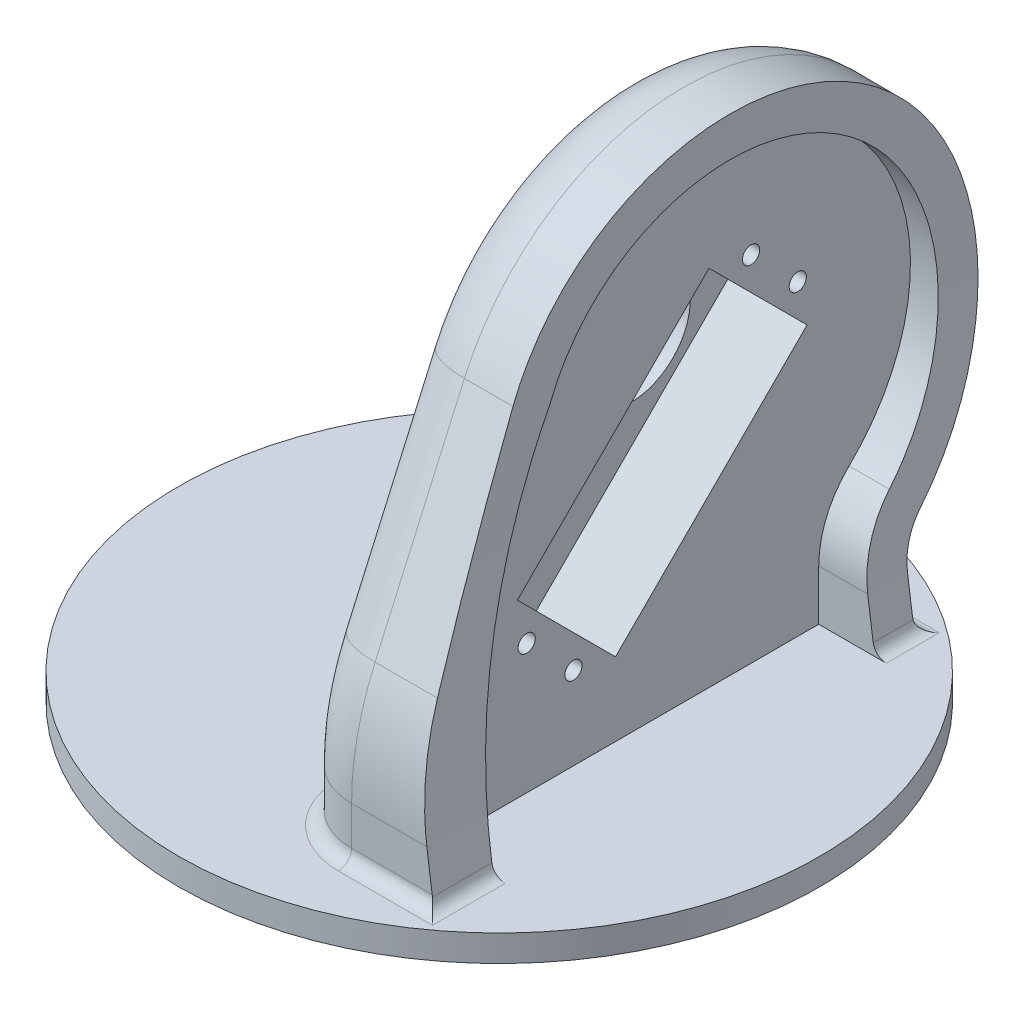
SolidWorks part; units mm, degrees
ref_plane "Front Plane" through (0, 0, 0) normal (0, 0, 1) x (1, 0, 0)
ref_plane "Top Plane" through (0, 0, 0) normal (0, 1, 0) x (1, 0, 0)
ref_plane "Right Plane" through (0, 0, 0) normal (1, 0, 0) x (0, 0, -1)
sketch "Sketch1" plane through (0, 0, 0) normal (0, 1, 0) x (1, 0, 0)
  line L0 (0, -7.25) -> (0, 7.25) construction
  circle A0 centre (0, 0) radius 48.5
  circle A1 centre (0, 7.25) radius 1.5
  circle A2 centre (0, -7.25) radius 1.5
  point P6 (0, 0)
  dimension "D2" = 97
  dimension "D3" = 3
  dimension "D1" = 14.5
extrude "Boss-Extrude3" add sketch "Sketch1" along normal blind 4
sketch "Sketch2" plane through (0, 4, 0) normal (0, 1, 0) x (1, 0, 0)
  line L0 (0, 11.1571) -> (0, -11.7638) construction
  circle A1 centre (0, 0) radius 3.75
  dimension "D1" = 7.5
sketch "Sketch3" plane through (0, 0, 0) normal (1, 0, 0) x (0, 0, -1)
  line L0 (30.34, 4) -> (-30.34, 4)
  line L1 (30.34, 4) -> (30.34, 11.64)
  line L2 (48.5, 4) -> (-48.5, 4) construction
  line L3 (-30.34, 4) -> (-30.34, 11.86)
  line L4 (-27.3065, 26.1616) -> (-13.7924, 56.5853)
  arc A0 (30.34, 11.64) -> (34.9356, 22.445) centre (45.34, 11.64) cw
  arc A1 (34.9356, 22.445) -> (-13.7924, 56.5853) centre (13.91, 44.28) ccw
  arc A2 (-30.34, 11.86) -> (-27.3065, 26.1616) centre (4.89, 11.86) cw
  circle A3 centre (13.91, 44.28) radius 9
  point P3 (0, 4)
  dimension "D3" = 15
  dimension "D5" = 35.23
  dimension "D6" = 18
  dimension "D1" = 60.68
  dimension "D2" = 7.64
  dimension "D4" = 7.86
  dimension "D7" = 13.91
  dimension "D8" = 40.28
extrude "Boss-Extrude4" add sketch "Sketch3" along normal blind 14 from offset 4
sketch "Sketch5" plane through (0, 0, 0) normal (1, 0, 0) x (0, 0, -1)
  line L0 (-0.41, 15.11) -> (28.5814, 44.1014)
  line L1 (-0.41, 15.11) -> (-15.2592, 29.9592)
  line L2 (28.5814, 44.1014) -> (13.7321, 58.9506)
  line L3 (-15.2592, 29.9592) -> (13.7321, 58.9506)
  line L4 (14.0857, 29.6057) -> (-0.7636, 44.4549) construction
  line L5 (48.5, 4) -> (-48.5, 4) construction
  line L6 (6.6611, 37.0303) -> (23.6316, 54.0009) construction
  line L7 (27.1672, 50.4653) -> (20.0961, 57.5364) construction
  circle A0 centre (27.1672, 50.4653) radius 1.3
  circle A1 centre (20.0961, 57.5364) radius 1.3
  circle A2 centre (-6.774, 16.5242) radius 1.3
  circle A3 centre (-13.845, 23.5953) radius 1.3
  point P14 (23.6316, 54.0009)
  dimension "D8" = 2.6
  dimension "D1" = 0.41
  dimension "D2" = 11.11
  dimension "D3" = 41
  dimension "D4" = 21
  dimension "D5" = 45
  dimension "D6" = 3.5
  dimension "D7" = 10
extrude "Cut-Extrude2" cut sketch "Sketch5" along normal through all from offset 6
sketch "Sketch9" plane through (18, 0, 0) normal (1, 0, 0) x (0, 0, -1)
  line L2 (-16.534, 57.8032) -> (-30.0482, 27.3795) construction
  line L4 (-30.34, 11.86) -> (-30.34, 4)
  line L5 (-30.34, 4) -> (30.34, 4)
  line L6 (30.34, 4) -> (30.34, 11.64)
  line L7 (-13.7924, 56.5853) -> (-27.3065, 26.1616)
  line L10 (30.34, 4) -> (30.34, 11.64)
  line L12 (-33.34, 1) -> (33.34, 1) construction
  line L13 (36.34, 4) -> (36.34, 11.64)
  line L14 (-19.2757, 59.021) -> (-32.7899, 28.5973)
  line L15 (-36.34, 11.86) -> (-36.34, 4)
  line L17 (48.5, 4) -> (-48.5, 4) construction
  line L19 (-36.34, 11.86) -> (-36.34, 1) construction
  line L20 (36.34, 1) -> (36.34, 11.64) construction
  line L21 (-33.34, 11.86) -> (-33.34, 1) construction
  line L22 (33.34, 1) -> (33.34, 11.64) construction
  line L24 (-30.34, 4) -> (30.34, 4) construction
  line L25 (-33.34, 11.86) -> (-33.34, 4) construction
  line L26 (33.34, 4) -> (33.34, 11.64) construction
  line L27 (-36.34, 4) -> (-27.34, 4)
  line L28 (30.34, 4) -> (36.34, 4)
  line L29 (-13.7924, 56.5853) -> (-27.3065, 26.1616) construction
  line L30 (-30.34, 11.86) -> (-30.34, 4) construction
  arc A0 (37.0165, 20.284) -> (33.34, 11.64) centre (45.34, 11.64) ccw construction
  arc A1 (37.0165, 20.284) -> (-16.534, 57.8032) centre (13.91, 44.28) ccw construction
  arc A2 (-30.0482, 27.3795) -> (-33.34, 11.86) centre (4.89, 11.86) ccw construction
  arc A3 (34.9356, 22.445) -> (30.34, 11.64) centre (45.34, 11.64) ccw
  arc A4 (34.9356, 22.445) -> (-13.7924, 56.5853) centre (13.91, 44.28) ccw
  arc A5 (-27.3065, 26.1616) -> (-30.34, 11.86) centre (4.89, 11.86) ccw
  arc A6 (34.9356, 22.445) -> (30.34, 11.64) centre (45.34, 11.64) ccw
  arc A7 (34.9356, 22.445) -> (-13.7924, 56.5853) centre (13.91, 44.28) ccw
  arc A9 (39.0973, 18.123) -> (36.34, 11.64) centre (45.34, 11.64) ccw
  arc A10 (39.0973, 18.123) -> (-19.2757, 59.021) centre (13.91, 44.28) ccw
  arc A11 (-32.7899, 28.5973) -> (-36.34, 11.86) centre (4.89, 11.86) ccw
  arc A12 (-13.7924, 56.5853) -> (-27.34, 4) centre (72.634, 6.2814) ccw
  arc A16 (-27.3065, 26.1616) -> (-30.34, 11.86) centre (4.89, 11.86) ccw construction
  dimension "D5" = 100
  dimension "D4" = 3
  dimension "D1" = 0
  dimension "D2" = 3
  dimension "D3" = 3
  dimension "D7" = 3
extrude "Boss-Extrude5" add sketch "Sketch9" along normal blind 9 and the other way up to surface (14 mm away) other way up to face at (4, 23.8443, -1.8168)
sketch "Sketch10" plane through (0, 0, 0) normal (0, 0, 1) x (1, 0, 0)
  line L0 (27, 80.5924) -> (21, 80.5924)
  line L1 (27, 80.5924) -> (4, 80.5924) construction
  line L2 (48.5, 4) -> (-48.5, 4) construction
  line L3 (26.5, 4) -> (27, 4)
  line L4 (27, 4) -> (27, 80.5924)
  arc A0 (21, 80.5924) -> (26.5, 4) centre (520.9933, 78.0026) ccw
  dimension "D3" = 500
  dimension "D1" = 6
  dimension "D2" = 0.5
extrude "Cut-Extrude3" cut sketch "Sketch10" against normal through all both and the other way through all
fillet "Fillet1" radius 10 6 edges at (4, 7.82, -36.34) (4, 15.1625, -37.058) (4, 7.93, 36.34) (4, 20.4149, 35.4427) (4, 43.8092, 26.0328) (4, 74.0194, -34.7464)
fillet "Fillet2" radius 2 7 edges at (20.25, 4, 36.34) (6.9289, 4, 33.4111) (20.25, 4, -36.34) (6.9289, 4, -33.4111) (26.5, 4, -33.34) (26.5, 4, 31.84) (4, 4, 0)
sketch "Sketch11" plane through (0, 0, 0) normal (0, -1, 0) x (1, 0, 0)
  line L0 (0, 11.7638) -> (0, -11.1571) construction
  circle A0 centre (0, 0) radius 3.75
extrude "Cut-Extrude4" cut sketch "Sketch11" against normal blind 2.6
